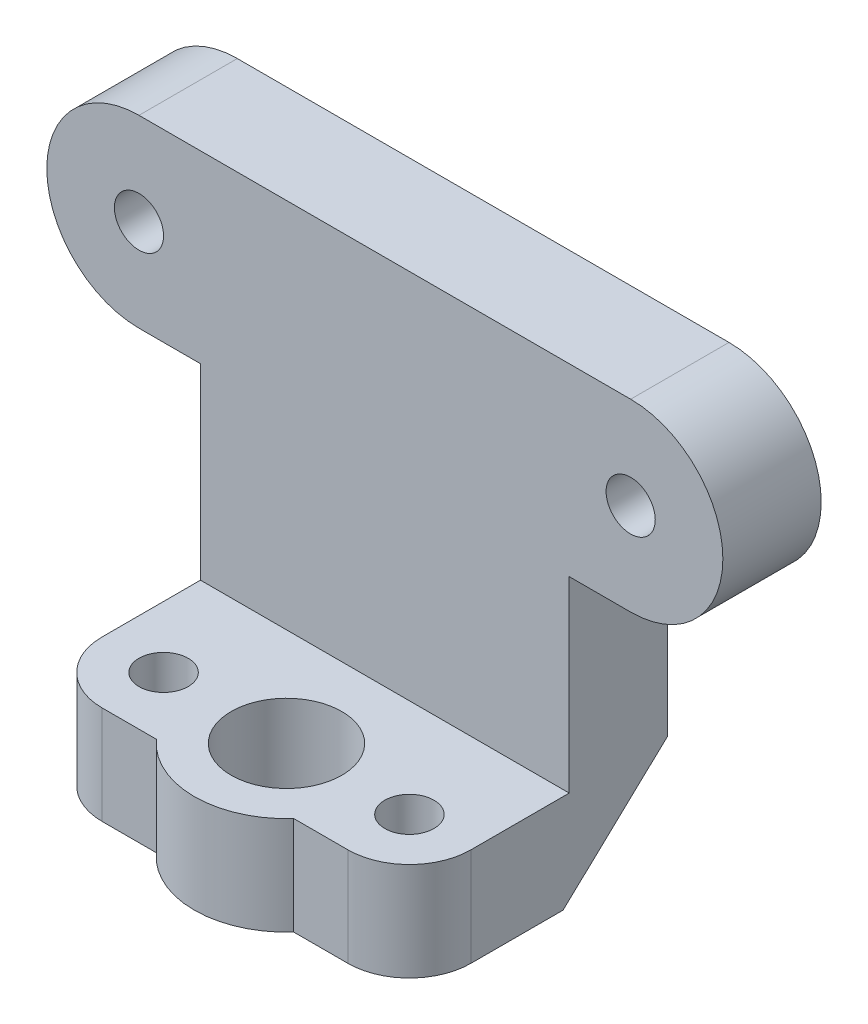
SolidWorks part; units mm, degrees
ref_plane "Front Plane" through (0, 0, 0) normal (0, 0, 1) x (1, 0, 0)
ref_plane "Top Plane" through (0, 0, 0) normal (0, 1, 0) x (1, 0, 0)
ref_plane "Right Plane" through (0, 0, 0) normal (1, 0, 0) x (0, 0, -1)
sketch "Sketch1" plane through (0, 0, 0) normal (0, 0, 1) x (1, 0, 0)
  line L0 (134.5, -11.85) -> (174.5, -11.85)
  line L1 (174.5, -26.85) -> (134.5, -26.85)
  arc A0 (134.5, -11.85) -> (134.5, -26.85) centre (134.5, -19.35) ccw
  arc A1 (174.5, -26.85) -> (174.5, -11.85) centre (174.5, -19.35) ccw
  circle A2 centre (134.5, -19.35) radius 2
  circle A3 centre (174.5, -19.35) radius 2
  dimension "D1" = 15
  dimension "D2" = 15
  dimension "D3" = 4
  dimension "D4" = 4
extrude "Boss-Extrude1" add sketch "Sketch1" along normal blind 8
sketch "Sketch2" plane through (0, -42.1, 0) normal (0, 1, 0) x (1, 0, 0)
  circle A0 centre (154.5, -16) radius 4.5
  circle A1 centre (154.5, -16) radius 7.5
  circle A2 centre (154.5, -16) radius 4 construction
  dimension "D1" = 15
  dimension "D2" = 0.5
extrude "Boss-Extrude2" add sketch "Sketch2" against normal blind 8 separate body
sketch "Sketch3" plane through (0, -42.1, 0) normal (0, 1, 0) x (1, 0, 0)
  line L0 (146.498, -16) -> (144.5, -16) construction
  line L1 (154.5, -16) -> (144.5, -16) construction
  line L2 (144.5, -11) -> (148.9098, -11)
  line L3 (144.5, -21) -> (148.9098, -21)
  line L4 (154.5, -16) -> (154.5, -18.2989) construction
  line L5 (162.502, -16) -> (164.5, -16) construction
  line L6 (162.502, -16) -> (164.5, -16) construction
  line L7 (164.5, -21) -> (160.0902, -21)
  line L8 (164.5, -11) -> (160.0902, -11)
  line L9 (146.498, -16) -> (144.5, -16) construction
  line L10 (146.498, -16) -> (144.5, -16) construction
  circle A0 centre (154.5, -16) radius 7.5 construction
  circle A1 centre (154.5, -16) radius 4.5 construction
  circle A2 centre (144.5, -16) radius 2
  arc A3 (144.5, -11) -> (144.5, -21) centre (144.5, -16) ccw
  arc A4 (148.9098, -11) -> (148.9098, -21) centre (154.5, -16) ccw
  arc A5 (160.0902, -11) -> (160.0902, -21) centre (154.5, -16) cw
  arc A6 (164.5, -11) -> (164.5, -21) centre (164.5, -16) cw
  circle A7 centre (164.5, -16) radius 2
  dimension "D2" = 4
  dimension "D3" = 5
  dimension "D1" = 10
extrude "Boss-Extrude3" add sketch "Sketch3" against normal blind 8
sketch "Sketch8" plane through (0, -26.85, 0) normal (0, -1, 0) x (-1, 0, 0)
  line L0 (-169.5, -8) -> (-169.5, 0)
  line L1 (-169.5, -16) -> (-169.5, 0) construction
  line L2 (-134.5, 0) -> (-174.5, 0) construction
  line L3 (-139.5, -16) -> (-139.5, 0) construction
  line L4 (-169.5, 0) -> (-139.5, 0)
  line L5 (-139.5, 0) -> (-139.5, -8)
  line L6 (-139.5, -8) -> (-169.5, -8)
  arc A0 (-164.5, -11) -> (-164.5, -21) centre (-164.5, -16) ccw construction
  arc A1 (-144.5, -21) -> (-144.5, -11) centre (-144.5, -16) ccw construction
extrude "Boss-Extrude7" add sketch "Sketch8" along normal up to surface (15.25 mm away) up to face at (154.5, -42.1, 20.5)
sketch "Sketch9" plane through (169.5, 0, 0) normal (1, 0, 0) x (0, 0, -1)
  line L0 (-8, -42.1) -> (-11, -42.1)
  line L1 (-11, -42.1) -> (-11, -50.1)
  line L2 (-11, -50.1) -> (-8.5, -50.1)
  line L3 (-8.5, -50.1) -> (0, -42.1)
  line L4 (0, -42.1) -> (-8, -42.1)
  line L5 (-8, -42.1) -> (-7.9465, -41.9509)
  line M2 (-8, -42.1) -> (0, -42.1)
extrude "Boss-Extrude8" add sketch "Sketch9" against normal up to surface (30 mm away) contours L2 L3 L0 L1 M2 region at (169.5, -45.2605, 7.179) up to face at (139.5, -34.475, 4)
sketch "Sketch10" plane through (0, -42.1, 0) normal (0, 1, 0) x (1, 0, 0)
  line L0 (139.5, -16) -> (139.5, -11)
  line L1 (139.5, -11) -> (144.5, -11)
  line L2 (144.5, -11) -> (139.5, -16)
  line L3 (139.5, -16) -> (139.4829, -15.9299)
  line L4 (154.5, -16) -> (154.5, -13.0837) construction
  line L5 (169.5, -16) -> (169.5171, -15.9299)
  line L6 (164.5, -11) -> (169.5, -16)
  line L7 (169.5, -11) -> (164.5, -11)
  line L8 (169.5, -16) -> (169.5, -11)
  line L9 (139.5, -16) -> (139.4829, -15.9299)
  arc A0 (144.5, -11) -> (144.5, -21) centre (144.5, -16) ccw construction
  line M4 (139.5, -11) -> (144.5, -11)
  arc M5 (144.5, -11) -> (144.5, -21) centre (144.5, -16) ccw
  arc M9 (164.5, -21) -> (164.5, -11) centre (164.5, -16) ccw
  line M10 (164.5, -11) -> (169.5, -11)
extrude "Boss-Extrude9" add sketch "Sketch10" against normal through all contours L0 M5 M4 | L8 M9 M10 region at (140.6168, -42.1, 12.1168) region at (168.3832, -42.1, 12.1168)
equation "\"X-ROD-SPACING\"=45"
equation "\"Y-ROD-SPACING\"=75"
equation "\"Z-ROD-SPACING\"=17.5"
equation "\"Y-BED-OFFSET\"=2"
equation "\"Y-BED-ROD-INSET\"=3.5"
equation "\"Y-BED-SCREW-SPACING\"=209"
equation "\"Y-BED-SCREW-CUTOUT-SLOT-HEIGHT\"=2"
equation "\"T-SLOT-NUT-FILLET-RADIUS\"=0.25"
equation "\"T-SLOT-SCREW-SHAFT-RADIUS\"=1.75"
equation "\"T-SLOT-SCREW-SHAFT-CUTOUT-LENGTH\"=10.5"
equation "\"T-SLOT-NUT-DEPTH\"=4.2"
equation "\"T-SLOT-NUT-WIDTH\"=3"
equation "\"T-SLOT-NUT-END-DISTANCE\"=8"
equation "\"ACRYLIC-THICKNESS\"=10"
equation "\"ACRYLIC-THICKNESS2\"=4.5"
equation "\"ACRYLIC-TAB-CUTOUT-SIZE\"=\"ACRYLIC-THICKNESS\"+\"ACRYLIC-TAB-TOLERANCE\"*2"
equation "\"ACRYLIC-TAB-TOLERANCE\"=.1"
equation "\"ACRYLIC-TAB-WIDTH\"=\"ACRYLIC-THICKNESS\""
equation "\"ACRYLIC-M3-HOLE\"=3.1"
equation "\"SMOOTHROD-CAP-SCREW-DISTANCE\"=20"
equation "\"FRAME-WIDTH-INNER\"=370"
equation "\"NEMA17-HOLE-SPACING\"=31"
equation "\"NEMA17-CENTRAL-CUTOUT\"=22.5"
equation "\"Z-BRACKET-REACH\"=55"
equation "\"Z-ROD-INSET\"=16"
equation "\"TOP-BRACKET-SPACING\"=40"
equation "\"SMOOTHROD-X-LENGTH\"=350"
equation "\"SMOOTHROD-Y-LENGTH\"=350"
equation "\"SMOOTHROD-Z-LENGTH\"=350"
equation "\"SMOOTHROD-TIGHTENING-HEADROOM\"=.25"
equation "\"LEADSCREW-Z-LENGTH\"=300"
equation "\"SCREW-LENGTH-FRAME\"=\"ACRYLIC-THICKNESS\" + 10"
equation "\"SCREW-LENGTH-MOTOR\"=\"ACRYLIC-THICKNESS\" + 5"
equation "\"SCREW-LENGTH-EXTRUDER\"=28"
equation "\"SCREW-HEAD-RADIUS\"=6"
equation "\"PRINTED-M3-HOLE\"=3.5"
equation "\"PRINTED-X-SMOOTHROD-DIAMETER\"=8.2"
equation "\"PRINTED-X-SMOOTHROD-CUTOUT\"=10"
equation "\"PRINTED-X-BASE-HEIGHT\"=10"
equation "\"PRINTED-LM8UU-CUTOUT-SIZE\"=15.25"
equation "\"PRINTED-LM8UU-CUTOUT-LENGTH\"=24.5"
equation "\"PRINTED-X-IDLER-HEIGHT\"=16"
equation "\"PRINTED-M3-NUT-AF\"=6.25"
equation "\"PSU-MOUNTING-WIDTH\"=95"
equation "\"PSU-MOUNTING-HEIGHT\"=177"
equation "\"Y-BELT-TO-ROD-DISTANCE\"=20"
equation "\"SPOOL-HOLDER-ROD-SPACING\"=150"
equation "\"ACRYLIC-X-CARRIAGE-WIDTH\"=55"
equation "\"ACRYLIC-X-CARRIAGE-HEIGHT\"=75"
equation "\"ACRYLIC-X-CARRIAGE-LM8UU-CUTOUT-WIDTH\"=24.25"
equation "\"ACRYLIC-X-CARRIAGE-LM8UU-CUTOUT-HEIGHT\"=11.5"
equation "\"ACRYLIC-X-CARRIAGE-SCREW-SPACING-X\"=15"
equation "\"ACRYLIC-X-CARRIAGE-SCREW-SPACING-Y\"=33"
equation "\"ACRYLIC-X-CARRIAGE-CENTER-TAB-SPACING\"=14"
equation "\"ACRYLIC-X-CARRIAGE-EXTRUDER-OFFSET\"=26"
equation "\"ACRYLIC-X-CARRIAGE-EXTRUDER-ANGLE\"=90"
equation "\"ACRYLIC-X-CARRIAGE-EXTRUDER-SHELF-DEPTH\"=\"ACRYLIC-X-CARRIAGE-EXTRUDER-OFFSET\" + 28"
equation "\"ACRYLIC-X-CARRIAGE-EXTRUDER-BRACE-SPACING\"=23"
equation "\"ACRYLIC-X-CARRIAGE-EXTRUDER-BRACE-TAB-OFFSET\"=20"
equation "\"ACRYLIC-X-CARRIAGE-EXTRUDER-BRACE-HEIGHT\"=35"
equation "\"ACRYLIC-X-CARRIAGE-EXTRUDER-BRACE-SCREW-SPACING\"=22"
equation "\"ACRYLIC-X-CARRIAGE-DUAL-WIDTH-MULTIPLIER\"=1.65"
equation "\"ACRYLIC-X-CARRIAGE-DUAL-HOTEND-SPACING\"=42"
equation "\"ACRYLIC-X-CARRIAGE-DUAL-WIDTH\"=75"
equation "\"ACRYLIC-X-CARRIAGE-DUAL-FAN-OFFSET\"=52"
equation "\"ACRYLIC-X-CARRIAGE-DUAL-FAN-HEIGHT\"=20"
equation "\"ACRYLIC-X-CARRIAGE-DUAL-HOTEND-SEPARATION\"=36"
equation "\"ACRYLIC-X-CARRIAGE-DUAL-MOUNT-PLATE-DEPTH\"=75"
equation "\"ACRYLIC-X-CARRIAGE-DUAL-MOUNT-BRACE-WIDTH\"=33"
equation "\"ACRYLIC-X-CARRIAGE-DUAL-MOUNT-SCREW-WIDTH\"=40"
equation "\"BLOWER-FAN-WIDTH\"=15"
equation "\"D2@Boss-Extrude2\"=\"SMOOTHROD-TIGHTENING-HEADROOM\""
equation "\"D1@Sketch3\"=\"SMOOTHROD-CAP-SCREW-DISTANCE\"/2"
